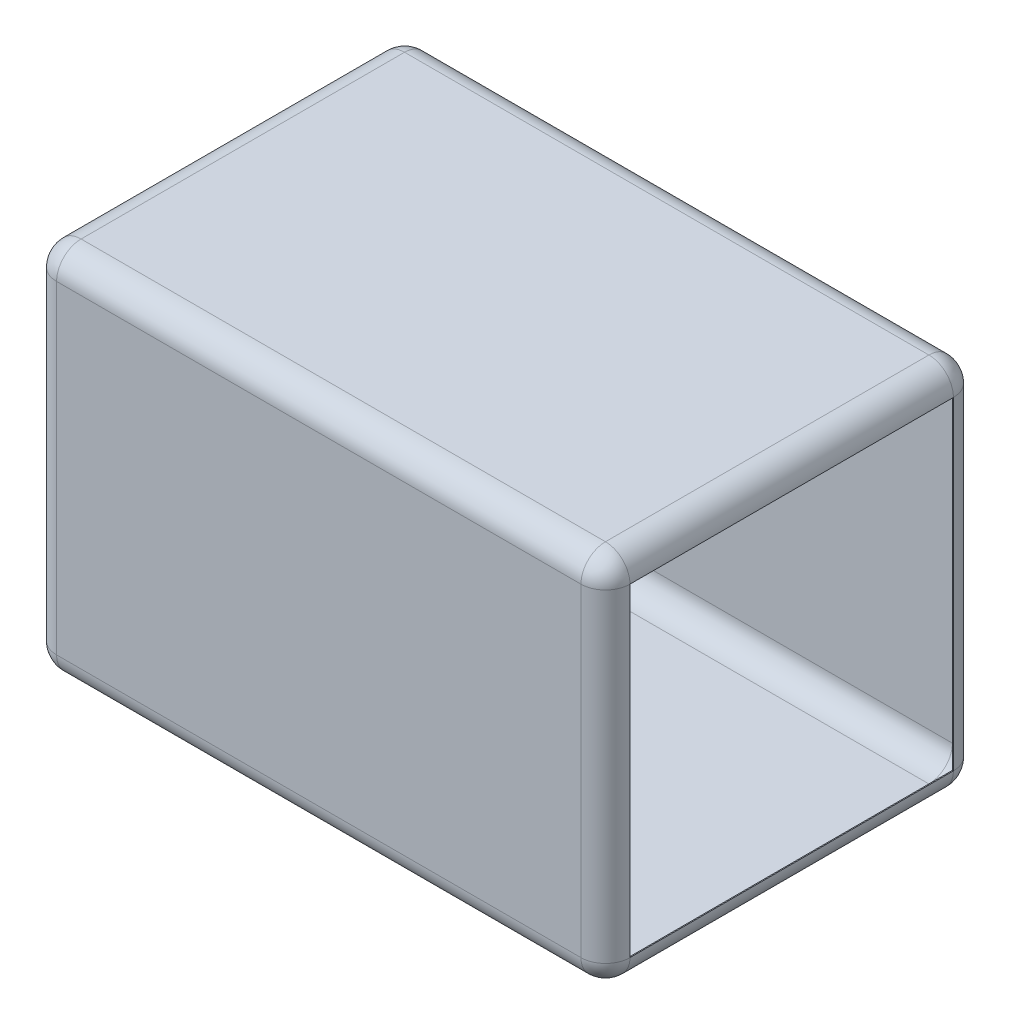
SolidWorks part; units mm, degrees
material "ABS"
ref_plane "Front Plane" through (0, 0, 0) normal (0, 0, 1) x (1, 0, 0)
ref_plane "Top Plane" through (0, 0, 0) normal (0, 1, 0) x (1, 0, 0)
ref_plane "Right Plane" through (0, 0, 0) normal (1, 0, 0) x (0, 0, -1)
sketch "Sketch4" plane through (0, 0, 0) normal (0, 1, 0) x (1, 0, 0)
  line L1 (58.5, -38) -> (-58.5, -38)
  line L2 (58.5, -38) -> (58.5, 38)
  line L3 (58.5, 38) -> (-58.5, 38)
  line L4 (-58.5, -38) -> (-58.5, 38)
  line L5 (58.5, -38) -> (-58.5, 38) construction
  line L6 (58.5, 38) -> (-58.5, -38) construction
  point P0 (0, 0)
  dimension "D1" = 76
  dimension "D2" = 117
extrude "Boss-Extrude3" add sketch "Sketch4" along normal blind 76
fillet "Fillet1" radius 5 12 edges at (58.5, 38, 38) (58.5, 38, -38) (0, 0, 38) (58.5, 0, 0) (0, 0, -38) (-58.5, 38, -38) (-58.5, 38, 38) (-58.5, 0, 0) (0, 76, -38) (58.5, 76, 0) (0, 76, 38) (-58.5, 76, 0)
shell "Shell1" thickness 0.2 removed face at (58.5, 38, 0)
